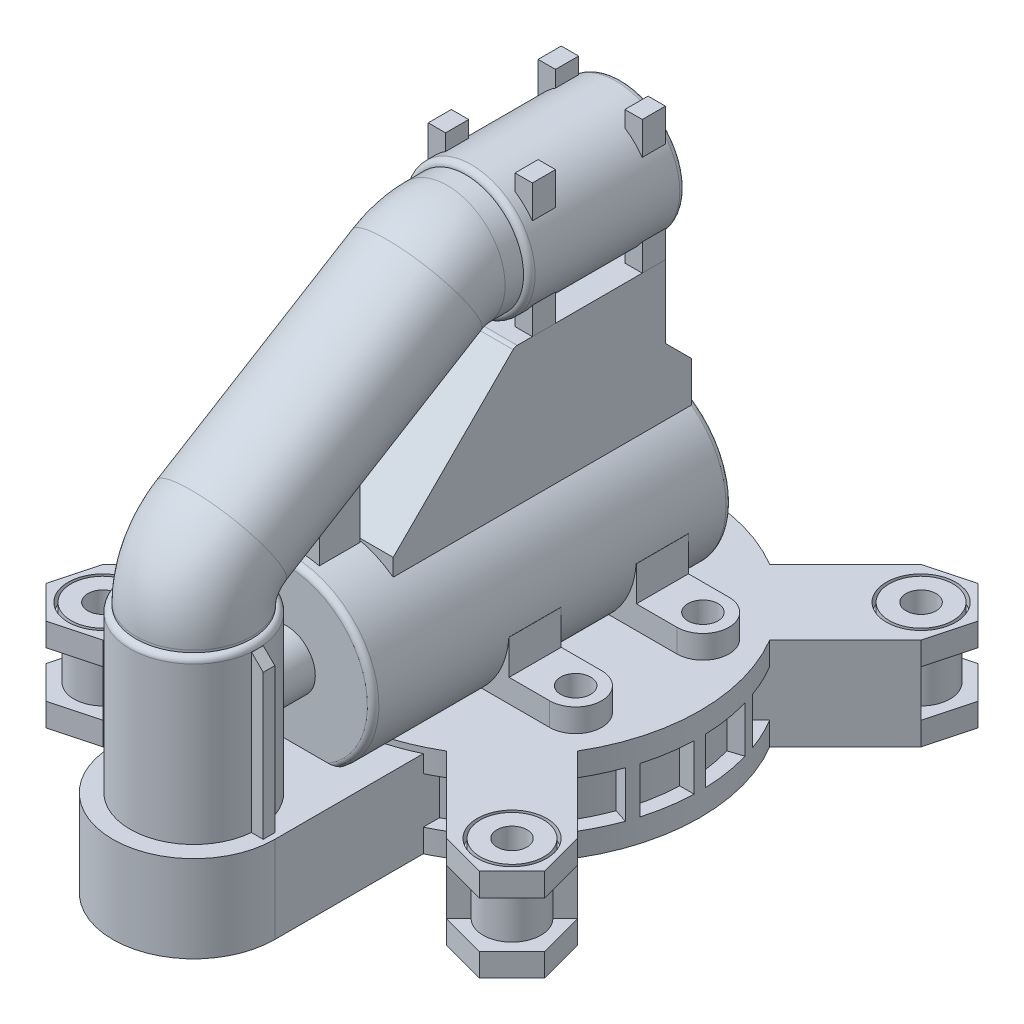
SolidWorks part; units mm, degrees
ref_plane "Front Plane" through (0, 0, 0) normal (0, 0, 1) x (1, 0, 0)
ref_plane "Top Plane" through (0, 0, 0) normal (0, 1, 0) x (1, 0, 0)
ref_plane "Right Plane" through (0, 0, 0) normal (1, 0, 0) x (0, 0, -1)
ref_plane "Plane3" through (0, 4, 0) normal (0, 1, 0) x (1, 0, 0)
ref_plane "Plane4" through (0, 12, 0) normal (0, 1, 0) x (1, 0, 0)
ref_plane "Plane5" through (0, 16, 0) normal (0, 1, 0) x (1, 0, 0)
sketch "Sketch11" plane through (0, 0, 0) normal (0, 1, 0) x (1, 0, 0)
  line L0 (27.9307, -16.617) -> (41.0122, -29.6985)
  line L1 (27.9307, 16.617) -> (41.0122, 29.6985)
  line L2 (16.617, 27.9307) -> (29.6985, 41.0122)
  line L3 (16.617, -27.9307) -> (29.6985, -41.0122)
  line L4 (-16.617, -27.9307) -> (-29.6985, -41.0122)
  line L5 (-27.9307, -16.617) -> (-41.0122, -29.6985)
  line L6 (-27.9307, 16.617) -> (-41.0122, 29.6985)
  line L7 (-16.617, 27.9307) -> (-29.6985, 41.0122)
  line L8 (43.0827, -37.4259) -> (41.0122, -29.6985)
  line L9 (37.4259, -43.0827) -> (43.0827, -37.4259)
  line L13 (41.0122, 29.6985) -> (43.0827, 37.4259)
  line L14 (43.0827, 37.4259) -> (37.4259, 43.0827)
  line L15 (37.4259, 43.0827) -> (29.6985, 41.0122)
  line L16 (30.4564, 30.4564) -> (33.2848, 27.6279) [skipped]
  line L17 (28.6632, 37.1485) -> (27.6279, 33.2848) [skipped]
  line L18 (37.1485, 28.6632) -> (41.0122, 29.6985) [skipped]
  line L19 (29.6985, -41.0122) -> (37.4259, -43.0827)
  line L20 (-37.4259, -43.0827) -> (-29.6985, -41.0122)
  line L21 (-43.0827, -37.4259) -> (-37.4259, -43.0827)
  line L22 (-41.0122, -29.6985) -> (-43.0827, -37.4259)
  line L23 (-43.0827, 37.4259) -> (-41.0122, 29.6985)
  line L24 (-37.4259, 43.0827) -> (-43.0827, 37.4259)
  line L25 (-29.6985, 41.0122) -> (-37.4259, 43.0827)
  arc A0 (16.617, 27.9307) -> (-16.617, 27.9307) centre (0, 0) ccw
  arc A1 (-27.9307, 16.617) -> (-27.9307, -16.617) centre (0, 0) ccw
  arc A2 (-16.617, -27.9307) -> (16.617, -27.9307) centre (0, 0) ccw
  arc A3 (27.9307, -16.617) -> (27.9307, 16.617) centre (0, 0) ccw
  point P23 (0, 0)
  point P46 (0, 0)
extrude "Boss-Extrude8" add sketch "Sketch11" along normal blind 4
sketch "Sketch12" plane through (0, 4, 0) normal (0, 1, 0) x (1, 0, 0)
  line L0 (38.8909, 31.8198) -> (41.0122, 29.6985)
  line L2 (26.1019, 14.7882) -> (41.0122, 29.6985)
  line L3 (14.7882, 26.1019) -> (29.6985, 41.0122)
  line L4 (29.6985, 41.0122) -> (31.8198, 38.8909)
  line L5 (26.1019, -14.7882) -> (41.0122, -29.6985)
  line L6 (41.0122, -29.6985) -> (38.8909, -31.8198)
  line L7 (31.8198, -38.8909) -> (29.6985, -41.0122)
  line L8 (14.7882, -26.1019) -> (29.6985, -41.0122)
  line L9 (-14.7882, -26.1019) -> (-29.6985, -41.0122)
  line L10 (-29.6985, -41.0122) -> (-31.8198, -38.8909)
  line L11 (-38.8909, -31.8198) -> (-41.0122, -29.6985)
  line L12 (-26.1019, -14.7882) -> (-41.0122, -29.6985)
  line L13 (-26.1019, 14.7882) -> (-41.0122, 29.6985)
  line L14 (-41.0122, 29.6985) -> (-38.8909, 31.8198)
  line L15 (-31.8198, 38.8909) -> (-29.6985, 41.0122)
  line L16 (-14.7882, 26.1019) -> (-29.6985, 41.0122)
  line L17 (-1, 32.4846) -> (-1, 29.9833)
  line L18 (10.9894, 30.5857) -> (10.2164, 28.2068)
  line L19 (1, 32.4846) -> (1, 29.9833)
  line L20 (9.0872, 31.2037) -> (8.3143, 28.8249)
  line L25 (31.2037, 9.0872) -> (28.8249, 8.3143)
  line L26 (30.5857, 10.9894) -> (28.2068, 10.2164)
  line L27 (32.4846, -1) -> (29.9833, -1)
  line L28 (32.4846, 1) -> (29.9833, 1)
  line L29 (30.5857, -10.9894) -> (28.2068, -10.2164)
  line L30 (31.2037, -9.0872) -> (28.8249, -8.3143)
  line L35 (9.0872, -31.2037) -> (8.3143, -28.8249)
  line L36 (10.9894, -30.5857) -> (10.2164, -28.2068)
  line L37 (-1, -32.4846) -> (-1, -29.9833)
  line L38 (1, -32.4846) -> (1, -29.9833)
  line L39 (-10.9894, -30.5857) -> (-10.2164, -28.2068)
  line L40 (-9.0872, -31.2037) -> (-8.3143, -28.8249)
  line L45 (-31.2037, -9.0872) -> (-28.8249, -8.3143)
  line L46 (-30.5857, -10.9894) -> (-28.2068, -10.2164)
  line L47 (-32.4846, 1) -> (-29.9833, 1)
  line L48 (-32.4846, -1) -> (-29.9833, -1)
  line L49 (-30.5857, 10.9894) -> (-28.2068, 10.2164)
  line L50 (-31.2037, 9.0872) -> (-28.8249, 8.3143)
  line L55 (-9.0872, 31.2037) -> (-8.3143, 28.8249)
  line L56 (-10.9894, 30.5857) -> (-10.2164, 28.2068)
  line L57 (-19.4257, 28.4385) -> (-12.3592, 18.7123) [skipped]
  line L58 (-21.0438, 27.263) -> (-13.9773, 17.5367) [skipped]
  line L59 (-27.263, 21.0438) -> (-17.5367, 13.9773) [skipped]
  line L60 (-28.4385, 19.4257) -> (-18.7123, 12.3592) [skipped]
  line L61 (19.4257, 28.4385) -> (12.3592, 18.7123) [skipped]
  line L62 (21.0438, 27.263) -> (13.9773, 17.5367) [skipped]
  line L63 (27.263, 21.0438) -> (17.5367, 13.9773) [skipped]
  line L64 (28.4385, 19.4257) -> (18.7123, 12.3592) [skipped]
  line L65 (27.263, -21.0438) -> (17.5367, -13.9773) [skipped]
  line L66 (28.4385, -19.4257) -> (18.7123, -12.3592) [skipped]
  line L67 (21.0438, -27.263) -> (13.9773, -17.5367) [skipped]
  line L68 (19.4257, -28.4385) -> (12.3592, -18.7123) [skipped]
  line L69 (-19.4257, -28.4385) -> (-12.3592, -18.7123) [skipped]
  line L70 (-21.0438, -27.263) -> (-13.9773, -17.5367) [skipped]
  line L71 (-27.263, -21.0438) -> (-17.5367, -13.9773) [skipped]
  line L72 (-28.4385, -19.4257) -> (-18.7123, -12.3592) [skipped]
  arc A0 (14.7882, 26.1019) -> (10.2164, 28.2068) centre (0, 0) ccw
  arc A1 (38.8909, 31.8198) -> (31.8198, 38.8909) centre (35.3553, 35.3553) ccw
  arc A2 (31.8198, -38.8909) -> (38.8909, -31.8198) centre (35.3553, -35.3553) ccw
  arc A3 (-38.8909, -31.8198) -> (-31.8198, -38.8909) centre (-35.3553, -35.3553) ccw
  arc A4 (-31.8198, 38.8909) -> (-38.8909, 31.8198) centre (-35.3553, 35.3553) ccw
  arc A5 (-26.1019, 14.7882) -> (-28.2068, 10.2164) centre (0, 0) ccw
  arc A6 (-14.7882, -26.1019) -> (-10.2164, -28.2068) centre (0, 0) ccw
  arc A7 (26.1019, -14.7882) -> (28.2068, -10.2164) centre (0, 0) ccw
  arc A8 (-31.2037, -9.0872) -> (-30.5857, -10.9894) centre (0, 0) ccw
  arc A9 (-32.4846, 1) -> (-32.4846, -1) centre (0, 0) ccw
  arc A10 (-30.5857, 10.9894) -> (-31.2037, 9.0872) centre (0, 0) ccw
  arc A11 (-10.9894, -30.5857) -> (-9.0872, -31.2037) centre (0, 0) ccw
  arc A12 (-28.8249, 8.3143) -> (-29.9833, 1) centre (0, 0) ccw
  arc A13 (-29.9833, -1) -> (-28.8249, -8.3143) centre (0, 0) ccw
  arc A14 (-28.2068, -10.2164) -> (-26.1019, -14.7882) centre (0, 0) ccw
  arc A15 (-9.0872, 31.2037) -> (-10.9894, 30.5857) centre (0, 0) ccw
  arc A16 (1, 32.4846) -> (-1, 32.4846) centre (0, 0) ccw
  arc A17 (10.9894, 30.5857) -> (9.0872, 31.2037) centre (0, 0) ccw
  arc A18 (31.2037, 9.0872) -> (30.5857, 10.9894) centre (0, 0) ccw
  arc A19 (32.4846, -1) -> (32.4846, 1) centre (0, 0) ccw
  arc A20 (30.5857, -10.9894) -> (31.2037, -9.0872) centre (0, 0) ccw
  arc A21 (-1, -32.4846) -> (1, -32.4846) centre (0, 0) ccw
  arc A22 (9.0872, -31.2037) -> (10.9894, -30.5857) centre (0, 0) ccw
  arc A23 (10.2164, -28.2068) -> (14.7882, -26.1019) centre (0, 0) ccw
  arc A24 (-8.3143, -28.8249) -> (-1, -29.9833) centre (0, 0) ccw
  arc A25 (28.8249, -8.3143) -> (29.9833, -1) centre (0, 0) ccw
  arc A26 (29.9833, 1) -> (28.8249, 8.3143) centre (0, 0) ccw
  arc A27 (28.2068, 10.2164) -> (26.1019, 14.7882) centre (0, 0) ccw
  arc A28 (-10.2164, 28.2068) -> (-14.7882, 26.1019) centre (0, 0) ccw
  arc A29 (-1, 29.9833) -> (-8.3143, 28.8249) centre (0, 0) ccw
  arc A30 (8.3143, 28.8249) -> (1, 29.9833) centre (0, 0) ccw
  arc A31 (1, -29.9833) -> (8.3143, -28.8249) centre (0, 0) ccw
  point P35 (0, 0)
  point P115 (0, 0)
  dimension "D1" = 20
  dimension "D2" = 4
extrude "Boss-Extrude10" add sketch "Sketch12" along normal blind 8
sketch "Sketch13" plane through (0, 12, 0) normal (0, 1, 0) x (1, 0, 0)
  line L0 (27.9307, -16.617) -> (41.0122, -29.6985)
  line L1 (43.0827, -37.4259) -> (41.0122, -29.6985)
  line L2 (27.9307, 16.617) -> (41.0122, 29.6985)
  line L3 (16.617, 27.9307) -> (29.6985, 41.0122)
  line L4 (37.4259, -43.0827) -> (43.0827, -37.4259)
  line L5 (41.0122, 29.6985) -> (43.0827, 37.4259)
  line L6 (43.0827, 37.4259) -> (37.4259, 43.0827)
  line L7 (37.4259, 43.0827) -> (29.6985, 41.0122)
  line L11 (27.6279, 33.2848) -> (30.4564, 30.4564) [skipped]
  line L12 (37.1485, 28.6632) -> (41.0122, 29.6985) [skipped]
  line L13 (29.6985, 41.0122) -> (28.6632, 37.1485) [skipped]
  line L14 (29.6985, -41.0122) -> (37.4259, -43.0827)
  line L15 (16.617, -27.9307) -> (29.6985, -41.0122)
  line L16 (-16.617, -27.9307) -> (-29.6985, -41.0122)
  line L17 (-37.4259, -43.0827) -> (-29.6985, -41.0122)
  line L18 (-43.0827, -37.4259) -> (-37.4259, -43.0827)
  line L19 (-41.0122, -29.6985) -> (-43.0827, -37.4259)
  line L20 (-27.9307, -16.617) -> (-41.0122, -29.6985)
  line L21 (-27.9307, 16.617) -> (-41.0122, 29.6985)
  line L22 (-43.0827, 37.4259) -> (-41.0122, 29.6985)
  line L23 (-37.4259, 43.0827) -> (-43.0827, 37.4259)
  line L24 (-29.6985, 41.0122) -> (-37.4259, 43.0827)
  line L25 (-16.617, 27.9307) -> (-29.6985, 41.0122)
  arc A0 (16.617, 27.9307) -> (-16.617, 27.9307) centre (0, 0) ccw
  arc A1 (-27.9307, 16.617) -> (-27.9307, -16.617) centre (0, 0) ccw
  arc A2 (-16.617, -27.9307) -> (16.617, -27.9307) centre (0, 0) ccw
  arc A3 (27.9307, -16.617) -> (27.9307, 16.617) centre (0, 0) ccw
  point P37 (0, 0)
extrude "Boss-Extrude11" add sketch "Sketch13" along normal blind 4
sketch "Sketch14" plane through (0, 0, 0) normal (0, 1, 0) x (1, 0, 0)
  line L0 (0, 0) -> (0, -55)
  line L1 (-14, -55) -> (-14, -20.7726)
  line L2 (14, -55) -> (14, -20.7726)
  line L3 (-14, -20.7726) -> (14, -20.7726)
  arc A0 (-14, -55) -> (14, -55) centre (0, -55) ccw
extrude "Boss-Extrude13" add sketch "Sketch14" along normal blind 15 contours L1 A0 L2 L3 region at (-13.4423, 0, 37.8863)
sketch "Sketch15" plane through (0, 12, 0) normal (0, 1, 0) x (1, 0, 0)
  line L1 (-13, -55) -> (-13, -56)
  line L4 (13, -55) -> (13, -56)
  line L5 (13, -56) -> (10.9545, -56)
  line L6 (-13, -55) -> (-13, -54)
  line L7 (-13, -54) -> (-10.9545, -54)
  line L8 (13, -54) -> (13, -55)
  line L9 (-10.9545, -56) -> (-13, -56)
  line L10 (10.9545, -54) -> (13, -54)
  arc A0 (10.9545, -54) -> (-10.9545, -54) centre (0, -55) ccw
  arc A1 (-10.9545, -56) -> (10.9545, -56) centre (0, -55) ccw
extrude "Boss-Extrude14" add sketch "Sketch15" along normal blind 30
sketch "Sketch16" plane through (0, 0, 0) normal (0, 0, 1) x (1, 0, 0)
  line L0 (0, 42) -> (0, 16)
  line L1 (10.9545, 42) -> (-10.9545, 42) construction
  line L2 (47.391, 16) -> (-47.391, 16) construction
  line L3 (0, 16) -> (0, 12)
  line L4 (47.391, 12) -> (-47.391, 12) construction
  circle A0 centre (0, 27) radius 15
extrude "Boss-Extrude16" add sketch "Sketch16" along normal blind 39 and the other way blind 23 contours L0 A0 L3 | L3 A0 L0 region at (6.3662, 27, 0) region at (-6.3662, 27, 0)
ref_plane "Plane6" through (0, 38, 0) normal (0, 1, 0) x (1, 0, 0)
sketch "Sketch17" plane through (0, 38, 0) normal (0, 1, 0) x (1, 0, 0)
  line L0 (-10.198, 17.5151) -> (-10.198, -29.535)
  line L2 (9, -29.535) -> (9, 17.5151)
  line L5 (-10.198, -29.535) -> (9, -29.535)
  line L6 (-10.198, 17.5151) -> (9, 17.5151)
extrude "Boss-Extrude18" add sketch "Sketch17" along normal blind 25
sketch "Sketch19" plane through (0, 0, 0) normal (1, 0, 0) x (0, 0, -1)
  line L0 (-29.535, 41.9801) -> (-8.5151, 63)
  line L1 (-29.535, 63) -> (-29.535, 39) construction
  line L2 (-29.535, 63) -> (17.5151, 63) construction
  line L3 (-8.5151, 63) -> (-29.535, 63)
  line L4 (-29.535, 63) -> (-29.535, 41.9801)
extrude "Cut-Extrude3" cut sketch "Sketch19" against normal blind 25 and the other way blind 25
ref_plane "Plane7" through (0, 63, 0) normal (0, 1, 0) x (1, 0, 0)
sketch "Sketch20" plane through (0, 0, 0) normal (0, 0, 1) x (1, 0, 0)
  line L0 (0, 63) -> (0, 85)
  line L1 (47.391, 63) -> (-47.391, 63) construction
  line L2 (0, 63) -> (0, 74)
  circle A0 centre (0, 74) radius 11
extrude "Boss-Extrude19" add sketch "Sketch20" along normal blind 8 and the other way blind 19 separate body contours L0 A0 | L0 A0 region at (-4.6685, 74, 0) region at (4.6685, 74, 0)
sketch "Sketch21" plane through (0, 38, 0) normal (0, 1, 0) x (1, 0, 0)
  circle A0 centre (0, -55) radius 11
extrude "Boss-Extrude20" add sketch "Sketch21" along normal blind 5
sketch "Sketch34" plane through (0, 0, 0) normal (1, 0, 0) x (0, 0, -1)
sketch "Sketch35" plane through (0, 0, 0) normal (1, 0, 0) x (0, 0, -1)
  line L0 (-55, 43) -> (-55, 43.3852)
  line L1 (-44, 43) -> (-66, 43) construction
  line L2 (-8, 74) -> (-11.1917, 74)
  line L3 (-8, 85) -> (-8, 63) construction
  line L4 (-16.3977, 72.538) -> (-50.2061, 51.9231)
  arc A0 (-55, 43.3852) -> (-50.2061, 51.9231) centre (-45, 43.3852) cw
  arc A1 (-11.1917, 74) -> (-16.3977, 72.538) centre (-11.1917, 64) ccw
  dimension "D1" = 10
sketch "Sketch54" plane through (0, 38, 0) normal (0, 1, 0) x (1, 0, 0)
  line L0 (0, -16.3977) -> (0, -50.2061) construction
  line L1 (-3.5, -29.8019) -> (3.5, -29.8019)
  line L2 (-3.5, -29.8019) -> (-3.5, -36.8019)
  line L3 (-3.5, -36.8019) -> (3.5, -36.8019)
  line L4 (3.5, -29.8019) -> (3.5, -36.8019)
  line L5 (-3.5, -29.8019) -> (3.5, -36.8019) construction
  line L6 (-3.5, -36.8019) -> (3.5, -29.8019) construction
  point P0 (0, -33.3019)
extrude "Boss-Extrude21" add sketch "Sketch54" along normal blind 29
sweep "Sweep21" add path "Sketch35" circular profile diameter 20 parameters "D3"=20
fillet "Fillet4" radius 1 1 edges at (0, 43, 66)
fillet "Fillet5" radius 1 1 edges at (11, 74, 8)
sketch "Sketch102" plane through (0, 63, 0) normal (0, 1, 0) x (1, 0, 0)
  line L0 (9, -8.5151) -> (9, 17.5151) construction
  line L1 (9, 17.5151) -> (9, 13.5151)
  line L2 (9, -5.4849) -> (6, -5.4849)
  line L3 (6, -5.4849) -> (6, -1.4849)
  line L4 (6, -1.4849) -> (9, -1.4849)
  line L5 (9, 17.5151) -> (6, 17.5151)
  line L6 (6, 17.5151) -> (6, 13.5151)
  line L7 (6, 13.5151) -> (9, 13.5151)
  line L8 (9, -1.4849) -> (9, -5.4849)
  line L11 (-9, -1.4849) -> (-9, -5.4849)
  line L12 (-6, 13.5151) -> (-9, 13.5151)
  line L13 (-6, 17.5151) -> (-6, 13.5151)
  line L14 (-9, 17.5151) -> (-6, 17.5151)
  line L15 (-6, -1.4849) -> (-9, -1.4849)
  line L16 (-6, -5.4849) -> (-6, -1.4849)
  line L17 (-9, -5.4849) -> (-6, -5.4849)
  line L18 (-9, 17.5151) -> (-9, 13.5151)
chamfer "Chamfer2" distance 2 angle 45 2 edges at (13, 42, 55) (-13, 42, 55)
fillet "Fillet6" radius 1 1 edges at (0, 42, 39)
fillet "Fillet7" radius 1 1 edges at (0, 42, -23)
ref_plane "Plane8" through (0, 0, 39) normal (0, 0, 1) x (1, 0, 0)
sketch "Sketch103" plane through (0, 0, 39) normal (0, 0, 1) x (1, 0, 0)
  circle A0 centre (0, 27) radius 5
extrude "Boss-Extrude27" add sketch "Sketch103" along normal blind 11
fillet "Fillet8" radius 1 1 edges at (-0.599, 63, 8.5151)
sketch "Sketch104" plane through (0, 16, 0) normal (0, 1, 0) x (1, 0, 0)
  line L1 (14, 23) -> (-14, 23) construction
  line L3 (5, 28) -> (-5, 28)
  line L4 (5, 28) -> (5, 23)
  line L5 (5, 23) -> (-5, 23)
  line L6 (-5, 28) -> (-5, 23)
  line L7 (5, 28) -> (-5, 23) construction
  line L8 (5, 23) -> (-5, 28) construction
  point P5 (0, 25.5)
extrude "Boss-Extrude28" add sketch "Sketch104" along normal blind 19
chamfer "Chamfer3" distance 5 angle 45 1 edges at (0, 35, -28)
sketch "Sketch106" plane through (0, 0, 0) normal (0, 0, 1) x (1, 0, 0)
  line L0 (9, 39) -> (9, 45.8333)
  line L3 (-10.198, 63) -> (-10.198, 38) construction
  line L4 (-10.198, 45.8333) -> (-10.198, 38)
  line L5 (47.391, 38) -> (-47.391, 38) construction
  line L6 (-10.198, 38) -> (9, 38)
  line L7 (9, 38) -> (9, 39)
  line L9 (9, 45.8333) -> (9, 51)
  line L10 (9, 63) -> (9, 39) construction
  line L11 (9, 51) -> (-10.198, 51)
  line L12 (-10.198, 51) -> (-10.198, 45.8333)
extrude "Boss-Extrude35" add sketch "Sketch106" against normal blind 22
chamfer "Chamfer6" distance 5 angle 45 1 edges at (-0.599, 51, -22)
sketch "Sketch107" plane through (0, 16, 0) normal (0, 1, 0) x (1, 0, 0)
  line L0 (32.5, 0) -> (15, 0)
  line L1 (-42.3487, 0) -> (42.3487, 0) construction
  line L2 (15, -38) -> (15, 22) construction
  line L3 (15, 6.5) -> (15, 11)
  line L4 (0, 28) -> (0, 23)
  line L5 (22, 6.5) -> (15, 6.5)
  line L6 (15, 6.5) -> (15, 15.5)
  line L7 (15, 15.5) -> (22, 15.5)
  line L8 (5, 28) -> (-5, 28) construction
  line L9 (-5, 23) -> (5, 23) construction
  line L10 (15, -15.5) -> (22, -15.5)
  line L11 (15, -6.5) -> (15, -15.5)
  line L12 (22, -6.5) -> (15, -6.5)
  line L13 (15, -6.5) -> (15, -11)
  line L14 (-15, -6.5) -> (-15, -11)
  line L15 (-22, -6.5) -> (-15, -6.5)
  line L16 (-15, -6.5) -> (-15, -15.5)
  line L17 (-15, -15.5) -> (-22, -15.5)
  line L18 (-15, 15.5) -> (-22, 15.5)
  line L19 (-15, 6.5) -> (-15, 15.5)
  line L20 (-22, 6.5) -> (-15, 6.5)
  line L21 (-15, 6.5) -> (-15, 11)
  line L22 (-32.5, 0) -> (-15, 0)
  arc A0 (27.9307, -16.617) -> (27.9307, 16.617) centre (0, 0) ccw construction
  arc A1 (22, 6.5) -> (22, 15.5) centre (22, 11) ccw
  arc A2 (22, -6.5) -> (22, -15.5) centre (22, -11) cw
  arc A3 (-22, -6.5) -> (-22, -15.5) centre (-22, -11) ccw
  arc A4 (-22, 6.5) -> (-22, 15.5) centre (-22, 11) cw
extrude "Boss-Extrude36" add sketch "Sketch107" along normal blind 4 contours L15 A3 L17 L16 L14 | A4 L20 L19 L18 | A2 L12 L11 L10 | L5 A1 L7 L6 L3 region at (20.315, 16, -11) region at (20.315, 16, 11) region at (-20.315, 16, 11) region at (-20.315, 16, -11)
sketch "Sketch108" plane through (0, 16, 0) normal (0, 1, 0) x (1, 0, 0)
  line L0 (-15, -15.5) -> (-10, -15.5)
  line L1 (-10, -11.1917) -> (-10, -16.3977) construction
  line L2 (-15, -6.5) -> (-10, -6.5)
  line L3 (-10, -6.5) -> (-10, -15.5)
  line L4 (-15, -15.5) -> (-15, -6.5)
  line L5 (-42.3487, 0) -> (42.3487, 0) construction
  line L6 (-10, 6.5) -> (-10, 15.5)
  line L7 (-15, 6.5) -> (-10, 6.5)
  line L8 (-15, 15.5) -> (-10, 15.5)
  line L9 (-15, 15.5) -> (-15, 6.5)
  line L10 (0, -47.3) -> (0, 47.3) construction
  line L11 (15, 15.5) -> (15, 6.5)
  line L12 (15, 15.5) -> (10, 15.5)
  line L13 (15, 6.5) -> (10, 6.5)
  line L14 (10, 6.5) -> (10, 15.5)
  line L15 (15, -15.5) -> (15, -6.5)
  line L16 (10, -6.5) -> (10, -15.5)
  line L17 (15, -6.5) -> (10, -6.5)
  line L18 (15, -15.5) -> (10, -15.5)
extrude "Boss-Extrude37" add sketch "Sketch108" along normal blind 10
sketch "Sketch109" plane through (0, 16, 0) normal (0, 1, 0) x (1, 0, 0)
  line L0 (-22, -6.5) -> (-22, -15.5)
  line L1 (-42.3487, 0) -> (42.3487, 0) construction
  line L2 (0, -47.3) -> (0, 47.3) construction
  circle A0 centre (-22, -11) radius 2.6
  circle A1 centre (-22, 11) radius 2.6
  circle A2 centre (22, -11) radius 2.6
  circle A3 centre (22, 11) radius 2.6
extrude "Cut-Extrude4" cut sketch "Sketch109" along normal blind 25 and the other way blind 12 contours A0 | A1 | A3 | A2
sketch "Sketch110" plane through (0, 16, 0) normal (0, 1, 0) x (1, 0, 0)
  line L0 (-41.0122, 29.6985) -> (-29.6985, 41.0122)
  circle A0 centre (-35.3553, 35.3553) radius 2.6
  circle A1 centre (35.3553, 35.3553) radius 2.6
  circle A2 centre (35.3553, -35.3553) radius 2.6
  circle A3 centre (-35.3553, -35.3553) radius 2.6
  point P15 (0, 0)
  dimension "D1" = 4
extrude "Cut-Extrude6" cut sketch "Sketch110" against normal blind 4 contours A0 | A1 | A3 | A2
sketch "Sketch111" plane through (0, 16, 0) normal (0, 1, 0) x (1, 0, 0)
  circle A0 centre (35.3553, 35.3553) radius 6
  circle A1 centre (35.3553, 35.3553) radius 5.5
  circle A2 centre (35.3553, -35.3553) radius 5.5
  circle A3 centre (35.3553, -35.3553) radius 6
  circle A4 centre (-35.3553, -35.3553) radius 5.5
  circle A5 centre (-35.3553, -35.3553) radius 6
  circle A6 centre (-35.3553, 35.3553) radius 5.5
  circle A7 centre (-35.3553, 35.3553) radius 6
  point P16 (0, 0)
  dimension "D1" = 4
extrude "Cut-Extrude7" cut sketch "Sketch111" against normal blind 2
ref_plane "Plane9" through (0, 0, -19) normal (0, 0, 1) x (1, 0, 0)
sketch "Sketch112" plane through (0, 0, -19) normal (0, 0, 1) x (1, 0, 0)
  line L0 (0, 85) -> (0, 63)
  line L1 (0, -47.3) -> (0, 47.3) construction
  line L2 (47.391, 63) -> (-47.391, 63) construction
  circle A0 centre (0, 74) radius 11 construction
  circle A1 centre (0, 74) radius 8
extrude "Boss-Extrude40" add sketch "Sketch102" along normal blind 23 separate body
extrude "Cut-Extrude9" cut sketch "Sketch112" along normal blind 15 contours L0 A1 | L0 A1 region at (3.3953, 74, -19) region at (-3.3953, 74, -19)
fillet "Fillet9" radius 1 1 edges at (11, 74, -19)
